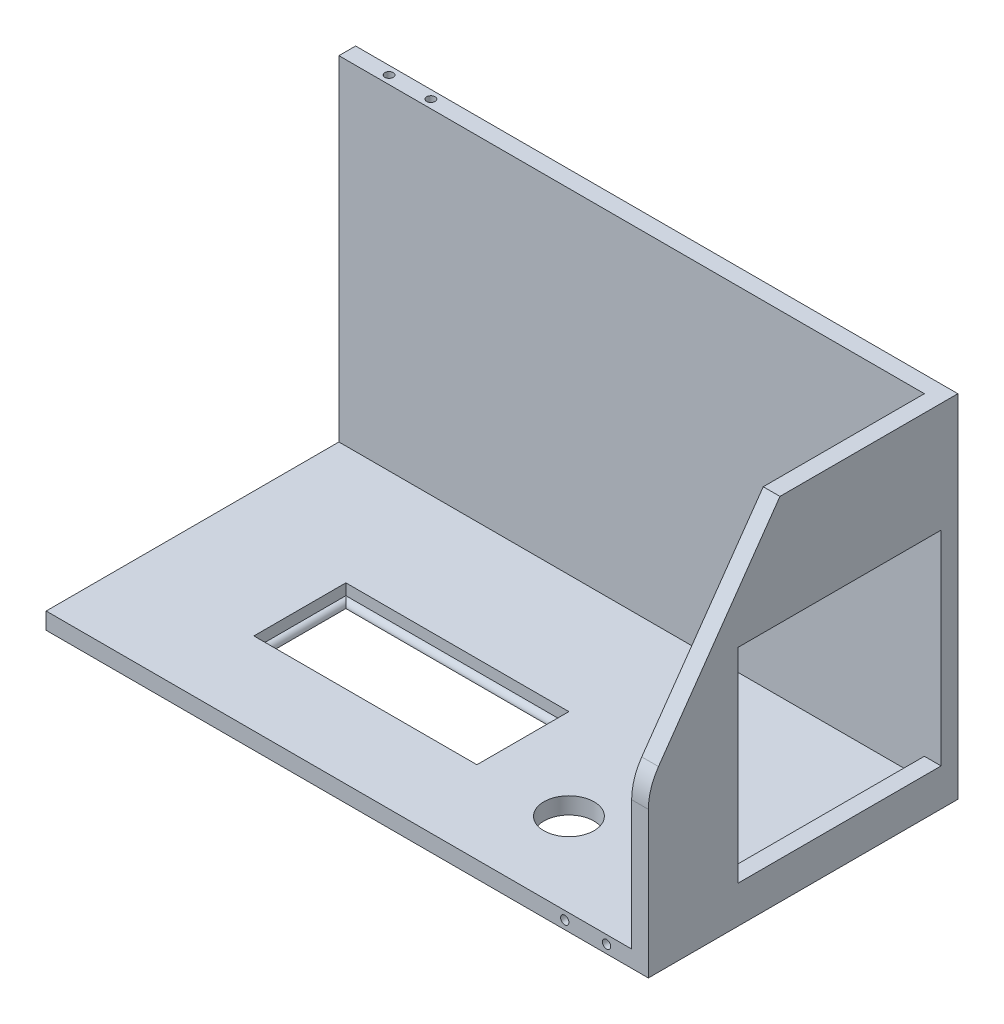
SolidWorks part; units mm, degrees
ref_plane "Front Plane" through (0, 0, 0) normal (0, 0, 1) x (1, 0, 0)
ref_plane "Top Plane" through (0, 0, 0) normal (0, 1, 0) x (1, 0, 0)
ref_plane "Right Plane" through (0, 0, 0) normal (1, 0, 0) x (0, 0, -1)
sketch "Sketch1" plane through (0, 0, 0) normal (0, 1, 0) x (1, 0, 0)
  line L0 (0, 0) -> (210, 0)
  line L1 (210, 0) -> (210, 105)
  line L2 (210, 105) -> (0, 105)
  line L3 (0, 105) -> (0, 0)
extrude "Boss-Extrude1" add sketch "Sketch1" along normal blind 6
sketch "Sketch2" plane through (0, 0, 0) normal (0, -1, 0) x (1, 0, 0)
  line L0 (0, -105) -> (210, -105)
  line L1 (210, -105) -> (210, -111)
  line L2 (210, -111) -> (0, -111)
  line L3 (0, -111) -> (0, -105)
extrude "Boss-Extrude2" add sketch "Sketch2" against normal blind 126
sketch "Sketch3" plane through (210, 0, 0) normal (1, 0, 0) x (0, 0, -1)
  line L0 (111, 126) -> (0, 126)
  line L1 (0, 126) -> (0, 0)
  line L2 (0, 0) -> (111, 0)
  line L3 (111, 0) -> (111, 126)
extrude "Boss-Extrude3" add sketch "Sketch3" along normal blind 6
sketch "Sketch6" plane through (216, 0, 0) normal (1, 0, 0) x (0, 0, -1)
  line L0 (0, 58.7) -> (47.2, 126)
  line L1 (0, 126) -> (0, 0) construction
  line L2 (111, 126) -> (0, 126) construction
  line L3 (47.2, 126) -> (0, 126)
  line L4 (0, 126) -> (0, 58.7)
  dimension "D1" = 58.7
  dimension "D2" = 63.8
extrude "Cut-Extrude2" cut sketch "Sketch6" against normal blind 6
sketch "Sketch7" plane through (0, 6, 0) normal (0, 1, 0) x (1, 0, 0)
  line L0 (0, 30) -> (210, 30) construction
  line L1 (0, 105) -> (0, 0) construction
  line L2 (210, 0) -> (210, 47.2) construction
  line L4 (0, 0) -> (210, 0) construction
  line L5 (105, 105) -> (105, 0) construction
  line L6 (210, 105) -> (0, 105) construction
  line L7 (105, 52.5) -> (210, 52.5) construction
  line L8 (210, 0) -> (210, 105) construction
  line L9 (157.5, 52.5) -> (157.5, 0) construction
  circle A0 centre (157.5, 30) radius 9
  dimension "D1" = 30
extrude "Cut-Extrude3" cut sketch "Sketch7" against normal blind 24
sketch "Sketch8" plane through (216, 0, 0) normal (1, 0, 0) x (0, 0, -1)
  line L0 (68.6, 126) -> (68.6, 0) construction
  line L1 (32.2, 86.625) -> (32.2, 13.375)
  line L2 (32.2, 13.375) -> (105, 13.375)
  line L3 (0, 50) -> (111, 50) construction
  line L4 (0, 58.7) -> (0, 0) construction
  line L5 (111, 0) -> (111, 126) construction
  line L6 (105, 86.625) -> (105, 13.375)
  line L7 (105, 86.625) -> (32.2, 86.625)
  line L8 (111, 126) -> (47.2, 126) construction
  line L9 (0, 0) -> (111, 0) construction
  dimension "D1" = 50
  dimension "D2" = 73.25
  dimension "D3" = 72.8
  dimension "D4" = 21.4
  dimension "D5" = 6
extrude "Cut-Extrude4" cut sketch "Sketch8" against normal blind 24
sketch "Sketch9" plane through (0, 6, 0) normal (0, 1, 0) x (1, 0, 0)
  line L0 (85, 105) -> (85, 0) construction
  line L1 (210, 105) -> (0, 105) construction
  line L3 (85, 30) -> (210, 30) construction
  line L4 (210, 0) -> (210, 47.2) construction
  line L5 (147.5, 30) -> (147.5, 105) construction
  line L6 (105, 46) -> (210, 46) construction
  line L8 (125, 62.5) -> (125, 29.5)
  line L9 (125, 62.5) -> (45, 62.5)
  line L10 (45, 62.5) -> (45, 29.5)
  line L11 (45, 29.5) -> (125, 29.5)
  dimension "D1" = 16
  dimension "D2" = 59
  dimension "D3" = 33
  dimension "D4" = 80
  dimension "D5" = 85
extrude "Cut-Extrude5" cut sketch "Sketch9" against normal blind 24
fillet "Fillet1" radius 20 1 edges at (213, 58.7, 0)
sketch "Sketch11" plane through (0, 0, 0) normal (0, -1, 0) x (1, 0, 0)
  line L0 (45, -29.5) -> (125, -29.5)
  line L1 (125, -29.5) -> (125, -62.5)
  line L2 (125, -62.5) -> (45, -62.5)
  line L3 (45, -62.5) -> (45, -29.5)
  line L4 (47, -31.5) -> (123, -31.5)
  line L5 (123, -31.5) -> (123, -60.5)
  line L6 (123, -60.5) -> (47, -60.5)
  line L7 (47, -60.5) -> (47, -31.5)
  dimension "D1" = 2
  dimension "D2" = 2
  dimension "D3" = 2
  dimension "D4" = 2
extrude "Boss-Extrude4" add sketch "Sketch11" against normal blind 2
fillet "Fillet2" radius 2 4 edges at (85, 2, -31.5) (123, 2, -46) (85, 2, -60.5) (47, 2, -46)
sketch "Sketch12" plane through (0, 0, 0) normal (0, 0, 1) x (1, 0, 0)
  line L0 (0, 3) -> (216, 3) construction
  line L1 (0, 6) -> (0, 0) construction
  line L2 (216, 52.3857) -> (216, 0) construction
  line L3 (201, 6) -> (201, 0) construction
  line L4 (210, 6) -> (0, 6) construction
  line L5 (0, 0) -> (216, 0) construction
  line L6 (186, 6) -> (186, 0) construction
  line L7 (0, 6) -> (210, 6) construction
  circle A0 centre (201, 3) radius 1.5
  circle A1 centre (186, 3) radius 1.5
  dimension "D1" = 15
  dimension "D2" = 15
extrude "Cut-Extrude6" cut sketch "Sketch12" against normal blind 20
sketch "Sketch13" plane through (0, 126, 0) normal (0, 1, 0) x (1, 0, 0)
  line L0 (0, 108) -> (216, 108) construction
  line L1 (0, 105) -> (0, 111) construction
  line L2 (216, 111) -> (216, 47.2) construction
  line L3 (15, 111) -> (15, 105) construction
  line L4 (0, 111) -> (216, 111) construction
  line L5 (210, 105) -> (0, 105) construction
  line L6 (30, 111) -> (30, 105) construction
  circle A0 centre (15, 108) radius 1.5
  circle A1 centre (30, 108) radius 1.5
  dimension "D1" = 15
  dimension "D2" = 15
extrude "Cut-Extrude7" cut sketch "Sketch13" against normal blind 25
